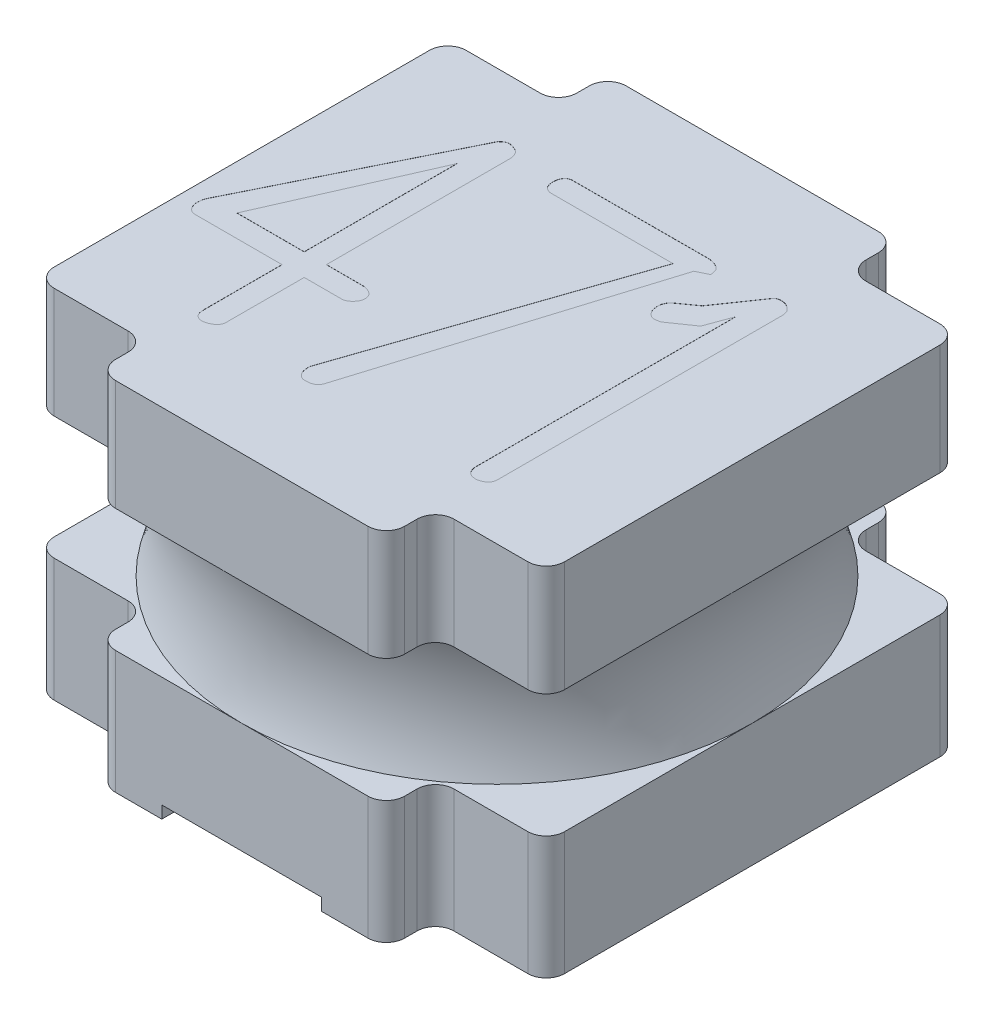
SolidWorks part; units mm, degrees
ref_plane "Front Plane" through (0, 0, 0) normal (0, 0, 1) x (1, 0, 0)
ref_plane "Top Plane" through (0, 0, 0) normal (0, 1, 0) x (1, 0, 0)
ref_plane "Right Plane" through (0, 0, 0) normal (1, 0, 0) x (0, 0, -1)
sketch "Sketch1" plane through (0, 0, 0) normal (0, 1, 0) x (1, 0, 0)
  line L0 (0, 6.4257) -> (0, -7.6623) construction
  line L1 (-1.025, 2.075) -> (1.025, 2.075)
  line L2 (-2.075, 1.525) -> (-2.075, -1.525)
  line L3 (-1.025, -2.075) -> (1.025, -2.075)
  line L4 (2.075, 1.525) -> (2.075, -1.525)
  line L5 (-1.675, 1.675) -> (1.675, -1.675) construction
  line L6 (-1.675, -1.675) -> (1.675, 1.675) construction
  line L7 (-1.175, 1.925) -> (-1.175, 1.825)
  line L8 (-1.325, 1.675) -> (-1.925, 1.675)
  line L9 (0, 0) -> (-4.3179, 0) construction
  line L10 (1.325, 1.675) -> (1.925, 1.675)
  line L11 (1.175, 1.925) -> (1.175, 1.825)
  line L12 (-1.325, -1.675) -> (-1.925, -1.675)
  line L13 (1.325, -1.675) -> (1.925, -1.675)
  line L14 (1.175, -1.925) -> (1.175, -1.825)
  line L15 (-1.175, -1.925) -> (-1.175, -1.825)
  line L16 (-2.075, 2.075) -> (-1.175, 2.075) construction
  line L17 (-2.075, 2.075) -> (-1.675, 1.675) construction
  line L18 (-2.075, 2.075) -> (-2.075, 1.675) construction
  line L19 (1.175, 2.075) -> (2.075, 2.075) construction
  line L20 (1.675, 1.675) -> (2.075, 2.075) construction
  line L21 (2.075, 2.075) -> (2.075, 1.675) construction
  line L22 (2.075, -1.675) -> (2.075, -2.075) construction
  line L23 (1.675, -1.675) -> (2.075, -2.075) construction
  line L24 (1.175, -2.075) -> (2.075, -2.075) construction
  line L25 (-2.075, -2.075) -> (-1.175, -2.075) construction
  line L26 (-2.075, -2.075) -> (-1.675, -1.675) construction
  line L27 (-2.075, -1.675) -> (-2.075, -2.075) construction
  arc A0 (2.075, -1.525) -> (1.925, -1.675) centre (1.925, -1.525) cw
  arc A1 (1.325, -1.675) -> (1.175, -1.825) centre (1.325, -1.825) ccw
  arc A2 (1.175, -1.925) -> (1.025, -2.075) centre (1.025, -1.925) cw
  arc A3 (-1.025, -2.075) -> (-1.175, -1.925) centre (-1.025, -1.925) cw
  arc A4 (-1.175, -1.825) -> (-1.325, -1.675) centre (-1.325, -1.825) ccw
  arc A5 (-1.925, -1.675) -> (-2.075, -1.525) centre (-1.925, -1.525) cw
  arc A6 (-2.075, 1.525) -> (-1.925, 1.675) centre (-1.925, 1.525) cw
  arc A7 (2.075, 1.525) -> (1.925, 1.675) centre (1.925, 1.525) ccw
  arc A8 (1.325, 1.675) -> (1.175, 1.825) centre (1.325, 1.825) cw
  arc A9 (1.175, 1.925) -> (1.025, 2.075) centre (1.025, 1.925) ccw
  arc A10 (-1.325, 1.675) -> (-1.175, 1.825) centre (-1.325, 1.825) ccw
  arc A11 (-1.175, 1.925) -> (-1.025, 2.075) centre (-1.025, 1.925) cw
  point P0 (0, 0)
  point P22 (0, 0)
  point P23 (0, 0)
  point P24 (0, 0)
  point P25 (0, 0)
  point P26 (0, 0)
  point P27 (0, 0)
  point P28 (0, 0)
  point P38 (1.175, -1.675)
  point P47 (-1.175, -1.675)
  point P59 (1.175, 1.675)
  point P65 (-1.175, 1.675)
  dimension "D5" = 0.15
  dimension "D1" = 4.15
  dimension "D2" = 2.35
  dimension "D3" = 1.675
  dimension "D4" = 4.15
extrude "Boss-Extrude1" add sketch "Sketch1" along normal blind 0.9
sketch "Sketch2" plane through (0, 0, 0) normal (0, 0, 1) x (1, 0, 0)
  line L0 (0, 0.9) -> (0, 1.9) construction
  line L1 (-1.025, 0.9) -> (1.025, 0.9) construction
  line L3 (0, 1.4) -> (-4.897, 1.4) construction
  line L4 (-2, 1.4) -> (-2, 3.3523) construction
  line L6 (-2.075, 0.9) -> (-2.075, 0) construction
  line L7 (-2.075, 1.9) -> (0, 1.9)
  line L8 (0, 1.9) -> (0, 0.9)
  line L9 (0, 0.9) -> (-2.075, 0.9)
  arc A0 (-2.075, 1.9) -> (-2.075, 0.9) centre (-3.7042, 1.4) cw
  dimension "D1" = 1
  dimension "D2" = 2
revolve "Revolve1" add sketch "Sketch2" angle 360 about L8
extrude "Boss-Extrude2" add sketch "Sketch1<2>" along normal blind 0.9 from surface starting at face at (-2.075, 1.9, 0)
sketch "Sketch1<2>" plane through (0, 0, 0) normal (0, 1, 0) x (1, 0, 0) same geometry as "Sketch1"
sketch "Sketch3" plane through (0, 0, 0) normal (0, 1, 0) x (1, 0, 0)
  line L0 (-2.075, -1.275) -> (2.075, -1.275) construction
  line L1 (-2.075, -1.525) -> (-2.075, 1.525) construction
  line L2 (2.075, 1.525) -> (2.075, -1.525) construction
  line L3 (-1.325, -1.675) -> (-1.925, -1.675) construction
  text T0 "471" font "SWSimp" height 2.5
  dimension "D1" = 0.4
extrude "Cut-Extrude1" cut sketch "Sketch3" against normal blind 0.001 from surface starting at face at (0, 2.8, 0)
sketch "Sketch4" plane through (0, 0, 0) normal (0, -1, 0) x (1, 0, 0)
  line L0 (-0.65, 2.075) -> (-0.65, -2.075)
  line L1 (-1.025, 2.075) -> (1.025, 2.075) construction
  line L2 (1.025, -2.075) -> (-1.025, -2.075) construction
  line L3 (0, 2.075) -> (0, -2.075) construction
  line L4 (-1.175, -1.925) -> (-1.175, -1.825) construction
  line L5 (-1.325, -1.675) -> (-1.925, -1.675) construction
  line L6 (-2.075, -1.525) -> (-2.075, 1.525) construction
  line L7 (-1.925, 1.675) -> (-1.325, 1.675) construction
  line L8 (-1.175, 1.825) -> (-1.175, 1.925) construction
  line L9 (-1.175, -1.925) -> (-1.175, -1.825)
  line L10 (-1.325, -1.675) -> (-1.925, -1.675)
  line L11 (-2.075, -1.525) -> (-2.075, 1.525)
  line L12 (-1.925, 1.675) -> (-1.325, 1.675)
  line L13 (-1.175, 1.825) -> (-1.175, 1.925)
  line L14 (-0.65, 2.075) -> (-1.025, 2.075)
  line L15 (-0.65, -2.075) -> (-1.025, -2.075)
  line L16 (0.65, 2.075) -> (0.65, -2.075)
  line L17 (0.65, 2.075) -> (1.025, 2.075)
  line L18 (1.175, 1.825) -> (1.175, 1.925)
  line L19 (1.925, 1.675) -> (1.325, 1.675)
  line L20 (2.075, -1.525) -> (2.075, 1.525)
  line L21 (1.325, -1.675) -> (1.925, -1.675)
  line L22 (1.175, -1.925) -> (1.175, -1.825)
  line L23 (0.65, -2.075) -> (1.025, -2.075)
  arc A0 (-1.175, -1.925) -> (-1.025, -2.075) centre (-1.025, -1.925) ccw construction
  arc A1 (-1.175, -1.825) -> (-1.325, -1.675) centre (-1.325, -1.825) ccw construction
  arc A2 (-2.075, -1.525) -> (-1.925, -1.675) centre (-1.925, -1.525) ccw construction
  arc A3 (-1.925, 1.675) -> (-2.075, 1.525) centre (-1.925, 1.525) ccw construction
  arc A4 (-1.325, 1.675) -> (-1.175, 1.825) centre (-1.325, 1.825) ccw construction
  arc A5 (-1.025, 2.075) -> (-1.175, 1.925) centre (-1.025, 1.925) ccw construction
  arc A6 (-1.175, -1.925) -> (-1.025, -2.075) centre (-1.025, -1.925) ccw
  arc A7 (-1.175, -1.825) -> (-1.325, -1.675) centre (-1.325, -1.825) ccw
  arc A8 (-2.075, -1.525) -> (-1.925, -1.675) centre (-1.925, -1.525) ccw
  arc A9 (-1.925, 1.675) -> (-2.075, 1.525) centre (-1.925, 1.525) ccw
  arc A10 (-1.325, 1.675) -> (-1.175, 1.825) centre (-1.325, 1.825) ccw
  arc A11 (-1.025, 2.075) -> (-1.175, 1.925) centre (-1.025, 1.925) ccw
  arc A12 (1.025, 2.075) -> (1.175, 1.925) centre (1.025, 1.925) cw
  arc A13 (1.325, 1.675) -> (1.175, 1.825) centre (1.325, 1.825) cw
  arc A14 (1.925, 1.675) -> (2.075, 1.525) centre (1.925, 1.525) cw
  arc A15 (2.075, -1.525) -> (1.925, -1.675) centre (1.925, -1.525) cw
  arc A16 (1.175, -1.825) -> (1.325, -1.675) centre (1.325, -1.825) cw
  arc A17 (1.175, -1.925) -> (1.025, -2.075) centre (1.025, -1.925) cw
  dimension "D1" = 1.3
extrude "Boss-Extrude3" add sketch "Sketch4" along normal blind 0.1
